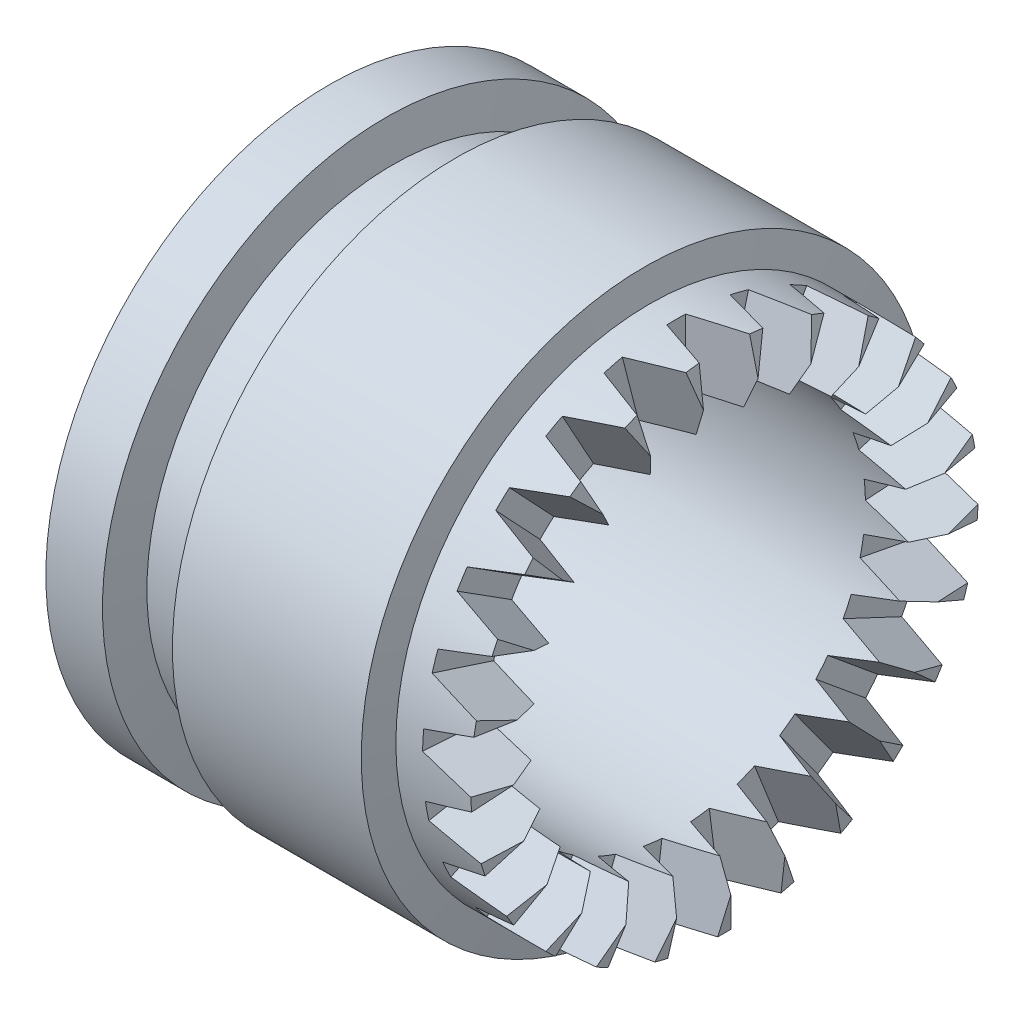
SolidWorks part; units mm, degrees
ref_plane "Front Plane" through (0, 0, 0) normal (0, 0, 1) x (1, 0, 0)
ref_plane "Top Plane" through (0, 0, 0) normal (0, 1, 0) x (1, 0, 0)
ref_plane "Right Plane" through (0, 0, 0) normal (1, 0, 0) x (0, 0, -1)
sketch "Sketch1" plane through (0, 0, 0) normal (0, 0, 1) x (1, 0, 0)
  line L0 (-31.6948, 0) -> (-53.6948, 0)
  line L1 (12.1, 0) -> (-12.1, 0) construction
  line L2 (-53.6948, 0) -> (-53.6948, 12.4176)
  line L3 (-53.2394, 15) -> (-50.2394, 15)
  line L4 (-31.6948, 10.0171) -> (-31.6948, 0)
  line L5 (-53.6948, 12.4176) -> (-53.2394, 15)
  line L6 (-50.2394, 15) -> (-49.8868, 13)
  line L7 (-49.8868, 13) -> (-46.8868, 13)
  line L8 (-46.8868, 13) -> (-46.5341, 15)
  line L9 (-36.5341, 15) -> (-36.2592, 13.4411)
  line L10 (-36.2592, 13.4411) -> (-32.2985, 13.4411)
  line L11 (-32.2985, 13.4411) -> (-31.6948, 10.0171)
  line L12 (-46.5341, 15) -> (-36.5341, 15)
  dimension "D1" = 22
  dimension "D2" = 15
  dimension "D3" = 10
  dimension "D4" = 3
  dimension "D5" = 3
  dimension "D6" = 10
  dimension "D7" = 100
  dimension "D8" = 100
  dimension "D9" = 2
  dimension "D10" = 100
  dimension "D11" = 10
revolve "Revolve1" add sketch "Sketch1" angle 360 about L0
sketch "Sketch2" plane through (-31.6948, 0, 0) normal (1, 0, 0) x (0, 0, -1)
  circle A1 centre (0, 0) radius 10.0171
  circle A2 centre (0, 0) radius 10.0171
  dimension "D1" = 0
extrude "Cut-Extrude1" cut sketch "Sketch2" against normal blind 19
sketch "Sketch3" plane through (-53.6948, 0, 0) normal (-1, 0, 0) x (0, 0, 1)
  circle A1 centre (0, 0) radius 12.4176
  circle A2 centre (0, 0) radius 12.4176
  dimension "D1" = 0
extrude "Cut-Extrude3" cut sketch "Sketch3" against normal blind 3
ref_plane "Plane1" through (-36.2592, 13.4411, 0) normal (0, 1, 0) x (1, 0, 0)
sketch "Sketch10" plane through (-36.2592, 13.4411, 0) normal (0, 1, 0) x (1, 0, 0)
  line L0 (4.5645, 0) -> (0, 0) construction
  line L1 (4.5645, 0) -> (-17.4355, 0) construction
  line L2 (3.9607, 0) -> (4.5645, 0) construction
  line L3 (0, 0) -> (3.9607, 0) construction
  line L4 (1.4104, 0.5) -> (4.5645, 1.5319)
  line L6 (4.5645, -1.5319) -> (1.4104, -0.5)
  line L7 (1.4104, -0.5) -> (1.4104, 0.5)
  line L8 (4.5645, -1.5319) -> (4.5645, 1.5319)
  line L9 (4.5645, 10.0171) -> (4.5645, -10.0171) construction
  dimension "D3" = 0.5
  dimension "D4" = 0.5
extrude "Cut-Extrude4" cut sketch "Sketch10" against normal blind 4
pattern_circular "CirPattern1" count 25 over 360 about axis through (-31.6948, 0, 0) along (-1, 0, 0) of "Cut-Extrude4"
